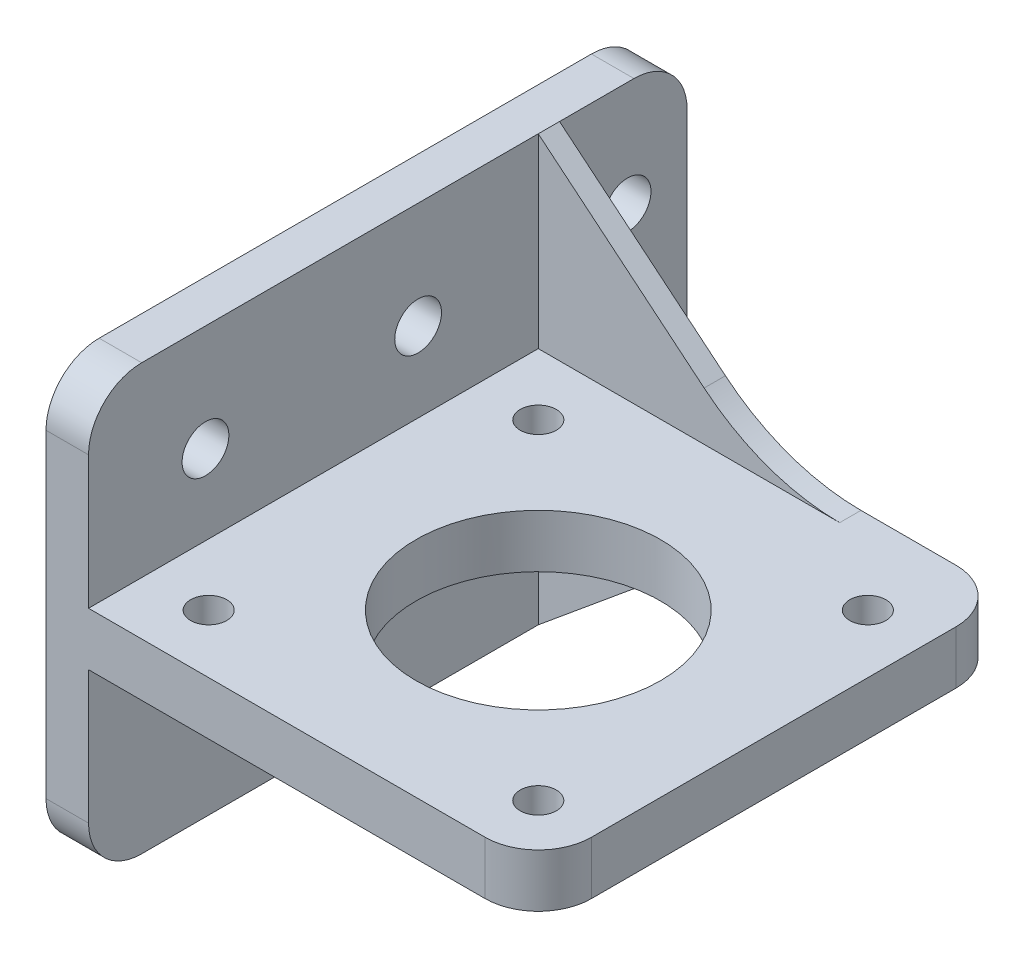
SolidWorks part; units mm, degrees
ref_plane "前视基准面" through (0, 0, 0) normal (0, 0, 1) x (1, 0, 0)
ref_plane "上视基准面" through (0, 0, 0) normal (0, 1, 0) x (1, 0, 0)
ref_plane "右视基准面" through (0, 0, 0) normal (1, 0, 0) x (0, 0, -1)
sketch "草图1" plane through (0, 0, 0) normal (0, 0, 1) x (1, 0, 0)
  line L0 (0, -2.5) -> (42.3, -2.5)
  line L1 (42.3, -2.5) -> (42.3, 2.5)
  line L2 (42.3, 2.5) -> (0, 2.5)
  line L3 (0, 2.5) -> (0, 20)
  line L4 (0, 20) -> (-4, 20)
  line L5 (-4, 20) -> (-4, -20)
  line L6 (-4, -20) -> (0, -20)
  line L7 (0, -20) -> (0, -2.5)
  line L8 (0, 2.5) -> (0, -2.5)
  line L9 (0, 0) -> (-4, 0) construction
  line L10 (0, 20) -> (21.15, 2.5)
  line L11 (21.15, -2.5) -> (0, -20)
  line L12 (21.15, 2.5) -> (21.15, -2.5)
  dimension "D1" = 40
  dimension "D2" = 4
  dimension "D3" = 5
  dimension "D4" = 42.3
  dimension "D5" = 17.5
extrude "凸台-拉伸1" add sketch "草图1" along normal blind 42.3 contours L8 L3 L4 L5 L6 L7 | L2 L8 L0 L1 | L9 L8 L3 L4 L5 | L2 L12 L0 L1 region at (10.575, 0, 0) region at (-2, -10, 0) region at (31.725, 0, 0) region at (-2, 10, 0)
sketch "草图2" plane through (0, 0, 0) normal (0, 1, 0) x (1, 0, 0)
  line L1 (42.3, -42.3) -> (0.3, -42.3) construction
  line L2 (42.3, -42.3) -> (42.3, -0.3) construction
  line L3 (42.3, -0.3) -> (0.3, -0.3) construction
  line L4 (0.3, -42.3) -> (0.3, -0.3) construction
  line L5 (42.3, -42.3) -> (0.3, -0.3) construction
  line L6 (42.3, -0.3) -> (0.3, -42.3) construction
  circle A0 centre (21.3, -21.3) radius 11.5
  circle A1 centre (36.8, -5.8) radius 1.7
  circle A2 centre (36.8, -36.8) radius 1.7
  circle A3 centre (5.8, -36.8) radius 1.7
  circle A4 centre (5.8, -5.8) radius 1.7
  point P21 (21.3, -21.3)
  dimension "D3" = 23
  dimension "D4" = 3.4
  dimension "D1" = 42
  dimension "D2" = 42
  dimension "D6" = 31
  dimension "D5" = 4
extrude "切除-拉伸1" cut sketch "草图2" along normal up to next and the other way up to next
extrude "凸台-拉伸2" add sketch "草图1<3>" against normal blind 2 contours L10 L3 L2 | L11 L0 L7 | L8 L9 L5 L6 L7 | L9 L8 L3 L4 L5 | L2 L8 L0 L1 | L2 L12 L0 L1 region at (10.575, 0, 0) region at (7.05, -8.3333, 0) region at (-2, -10, 0) region at (31.725, 0, 0) region at (-2, 10, 0) region at (7.05, 8.3333, 0)
sketch "草图1<3>" plane through (0, 0, 0) normal (0, 0, 1) x (1, 0, 0) same geometry as "草图1"
extrude "凸台-拉伸3" add sketch "草图1<4>" against normal blind 12 from surface contours L9 L8 L3 L4 L5 | L8 L9 L5 L6 L7 region at (-2, -10, 0) region at (-2, 10, 0) starting at face at (14.8625, 0, -2)
sketch "草图1<4>" plane through (0, 0, 0) normal (0, 0, 1) x (1, 0, 0) same geometry as "草图1"
sketch "草图4" plane through (0, 0, 0) normal (1, 0, 0) x (0, 0, -1)
  line L0 (-1000, 0) -> (49000, 0) construction
  line L1 (-21.3, -995.5) -> (-21.3, 49004.5) construction
  line L3 (-1.45, -1006.5515) -> (-1.45, 48993.4485) construction
  circle A0 centre (8.4, 10) radius 2.2
  circle A1 centre (8.4, -10) radius 2.2
  circle A2 centre (-11.3, 10) radius 2.2
  circle A3 centre (-11.3, -10) radius 2.2
  circle A4 centre (-31.3, 10) radius 2.2
  circle A5 centre (-31.3, -10) radius 2.2
  dimension "D3" = 4.4
  dimension "D1" = 8.4
  dimension "D2" = 5.6
  dimension "D4" = 20
  dimension "D5" = 20
  dimension "D6" = 21.3
extrude "切除-拉伸2" cut sketch "草图4" against normal up to next
fillet "圆角1" radius 5 6 edges at (-2, 20, 42.3) (-2, -20, 42.3) (-2, 20, -14) (-2, -20, -14) (42.3, 0, 42.3) (42.3, 0, -2)
fillet "圆角2" radius 20 2 edges
